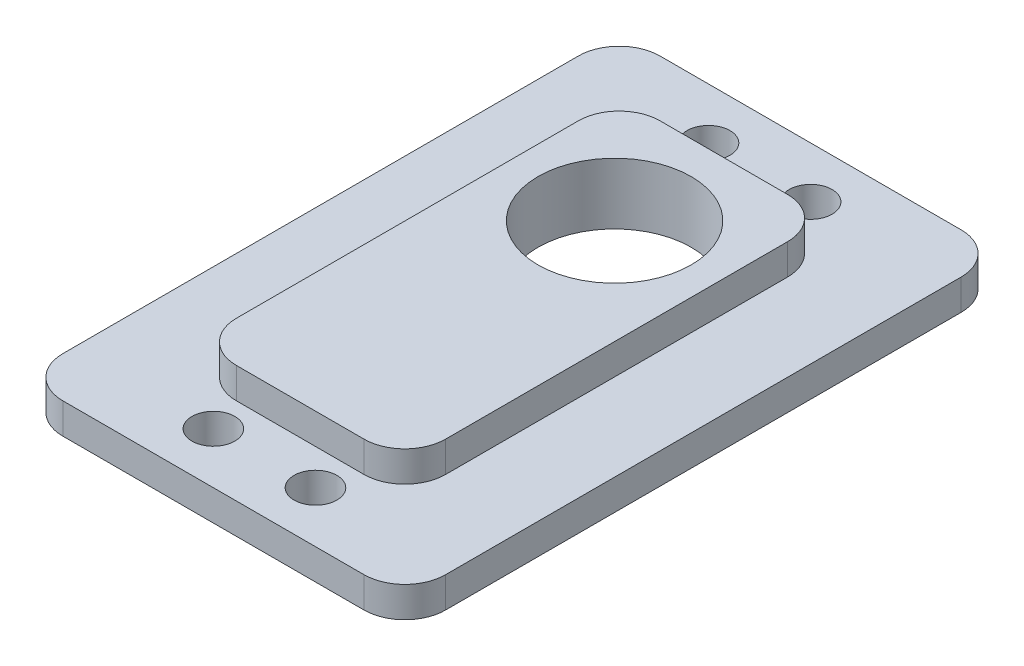
SolidWorks part; units mm, degrees
ref_plane "Front Plane" through (0, 0, 0) normal (0, 0, 1) x (1, 0, 0)
ref_plane "Top Plane" through (0, 0, 0) normal (0, 1, 0) x (1, 0, 0)
ref_plane "Right Plane" through (0, 0, 0) normal (1, 0, 0) x (0, 0, -1)
sketch "Sketch1" plane through (0, 0, 0) normal (0, 1, 0) x (1, 0, 0)
  line L5 (-10.75, 11.2) -> (10.75, 11.2) construction
  line L12 (-10.75, 11.2) -> (-10.75, -31.3) construction
  line L13 (-10.75, -31.3) -> (10.75, -31.3) construction
  line L14 (10.75, 11.2) -> (10.75, -31.3) construction
  line L24 (-10.25, -30.8) -> (10.25, -30.8)
  line L25 (10.25, 10.7) -> (10.25, -30.8)
  line L26 (-18.75, 19.2) -> (18.75, 19.2)
  line L27 (-18.75, 19.2) -> (-18.75, -39.3)
  line L28 (-18.75, -39.3) -> (18.75, -39.3)
  line L29 (18.75, 19.2) -> (18.75, -39.3)
  line L30 (0, -39.3) -> (0, 19.2) construction
  line L31 (-18.75, -10.05) -> (18.75, -10.05) construction
  line L32 (-10.25, 10.7) -> (10.25, 10.7)
  line L33 (-10.25, 10.7) -> (-10.25, -30.8)
  circle A2 centre (5, 14.2) radius 2.1
  circle A3 centre (-5, 14.2) radius 2.1
  circle A4 centre (-5, -34.3) radius 2.1
  circle A5 centre (5, -34.3) radius 2.1
  circle A9 centre (0, 0) radius 7 construction
  circle A10 centre (0, 0) radius 7.5
  point P4 (0, 0)
  point P5 (-2.8825, 14.2)
  point P6 (-5, 14.2)
  point P7 (0, 0)
  point P8 (-5.1738, 14.2)
  point P9 (0, 11.2)
  point P10 (-5, -36.1479)
  point P352 (0, -10.05)
  dimension "D3" = 10.75
  dimension "D15" = 4.2
  dimension "D26" = 14
  dimension "D12" = 8
  dimension "D4" = 3
  dimension "D5" = 5
  dimension "D6" = 8
  dimension "D7" = 42.5
  dimension "D8" = 21.5
  dimension "D9" = 3
  dimension "D10" = 8
  dimension "D11" = 10
  dimension "D13" = 0.5
  dimension "D14" = 10
  dimension "D16" = 0.5
  dimension "D27" = 14.2
extrude "Boss-Extrude2" add sketch "Sketch1" along normal blind 6 contours L14 L5 L12 L13 | L24 L25 L32 L33 | A10
extrude "Boss-Extrude3" add sketch "Sketch1<3>" along normal blind 3 contours L29 L26 L27 L28 A5 A4 A3 A2 L5 L14 L13 L12 region at (0, 0, -18.5051)
sketch "Sketch1<3>" plane through (0, 0, 0) normal (0, 1, 0) x (1, 0, 0) same geometry as "Sketch1"
fillet "Fillet1" radius 4 8 edges at (-18.75, 1.5, -19.2) (18.75, 1.5, -19.2) (18.75, 1.5, 39.3) (-18.75, 1.5, 39.3) (-10.25, 4.5, -10.7) (10.25, 4.5, -10.7) (10.25, 4.5, 30.8) (-10.25, 4.5, 30.8)
